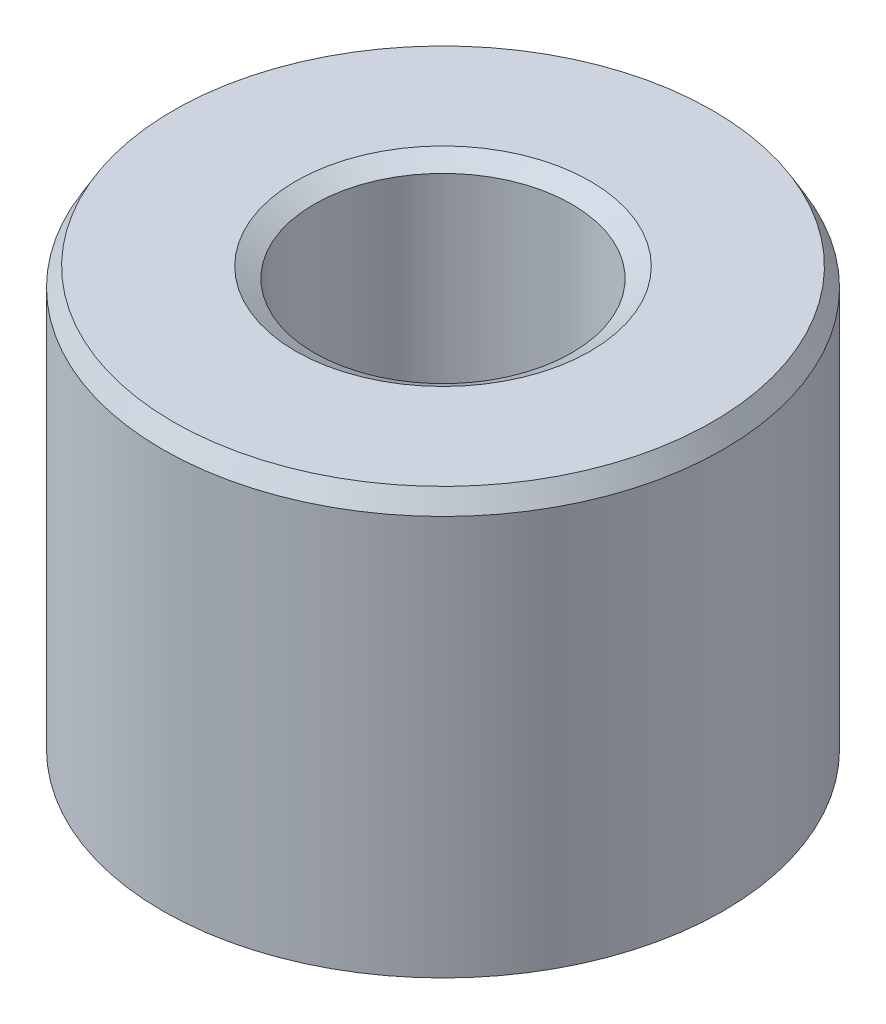
SolidWorks part; units mm, degrees
ref_plane "Front Plane" through (0, 0, 0) normal (0, 0, 1) x (1, 0, 0)
ref_plane "Top Plane" through (0, 0, 0) normal (0, 1, 0) x (1, 0, 0)
ref_plane "Right Plane" through (0, 0, 0) normal (1, 0, 0) x (0, 0, -1)
sketch "Sketch1" plane through (0, 0, 0) normal (0, 1, 0) x (1, 0, 0)
  circle A0 centre (0, 0) radius 10
  dimension "SLEEVE_OD" = 20
extrude "Boss-Extrude1" add sketch "Sketch1" along normal blind 15.2945
sketch "Sketch2" plane through (0, 0, 0) normal (0, 1, 0) x (1, 0, 0)
  circle A0 centre (0, 0) radius 4.5933
  dimension "BORE_D" = 9.1867
extrude "Cut-Extrude1" cut sketch "Sketch2" along normal through all
chamfer "Chamfer1" distance 0.6599 angle 30 4 edges at (0, 15.2945, 4.5933) (0, 0, 4.5933) (0, 0, 10) (0, 15.2945, 10) first distance on face at (0, 15.2945, 4.5933) first distance on face at (0, 0, 4.5933) first distance on face at (0, 15.2945, 10)
